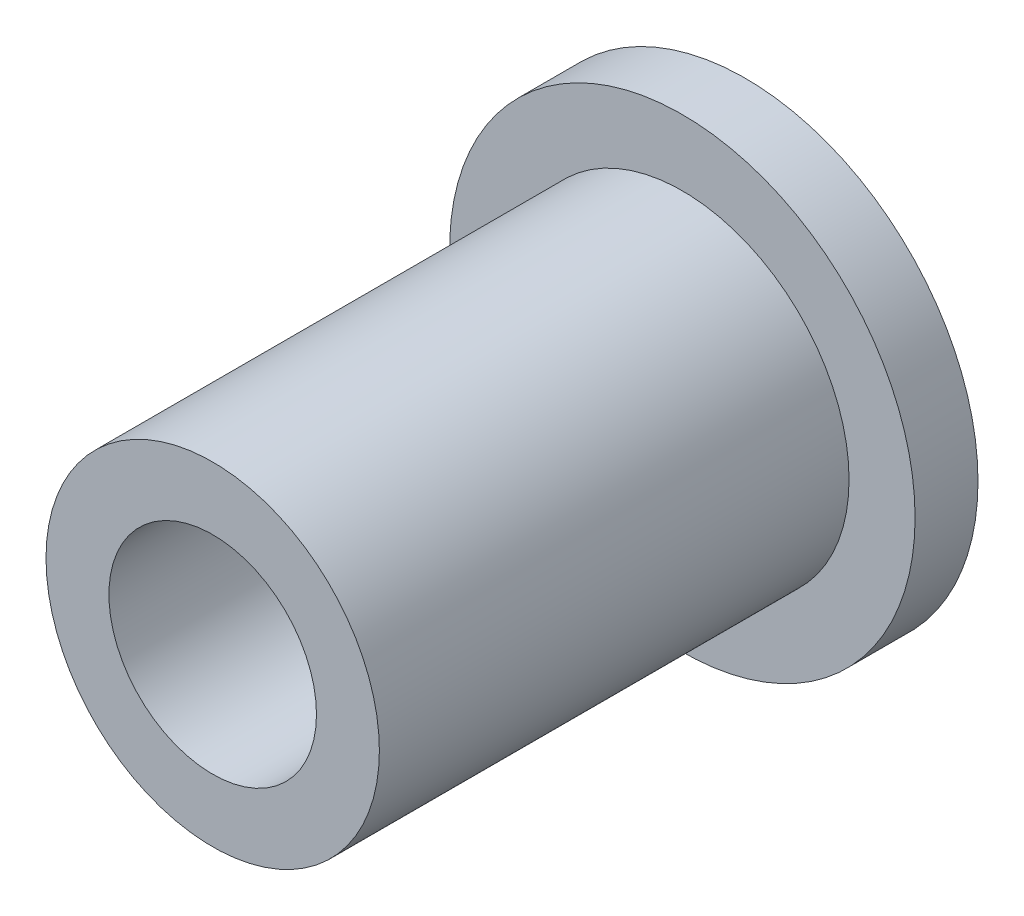
SolidWorks part; units mm, degrees
ref_plane "Front Plane" through (0, 0, 0) normal (0, 0, 1) x (1, 0, 0)
ref_plane "Top Plane" through (0, 0, 0) normal (0, 1, 0) x (1, 0, 0)
ref_plane "Right Plane" through (0, 0, 0) normal (1, 0, 0) x (0, 0, -1)
sketch "Sketch1" plane through (0, 0, 0) normal (0, 0, 1) x (1, 0, 0)
  circle A0 centre (0, 0) radius 5.55
  dimension "D1" = 11.1
base flange "Base-Flange1" sketch "Sketch1" thickness 1.5 reverse thickness direction no parameters "D1"=1
sketch "Sketch9" plane through (0, 0, 0) normal (0, 0, 1) x (1, 0, 0)
  circle A0 centre (0, 0) radius 3.975
  circle A1 centre (0, 0) radius 2.475
  dimension "D1" = 7.95
  dimension "D2" = 1.5
extrude "Boss-Extrude1" add sketch "Sketch9" along normal blind 11.2
sketch "Sketch11" plane through (0, 0, 0) normal (0, 0, 1) x (1, 0, 0)
  circle A0 centre (0, 0) radius 2.475
extrude "Cut-Extrude1" cut sketch "Sketch11" against normal through all normal cut yes
sketch "Bend-Lines1" plane through (0, 0, 0) normal (0, 1, 0) x (1, 0, 0)
sketch "Bounding-Box1" plane through (0, 0, 0) normal (0, 1, 0) x (1, 0, 0)
sheet metal parameters "Sheet-Metal(1)" thickness 1.5 parameters "D1"=1
flat pattern "Flat-Pattern(1)" [suppressed]
sketch "Bend-Lines2" plane through (0, 0, 0) normal (0, 1, 0) x (1, 0, 0)
sketch "Bounding-Box2" [suppressed] plane through (0, 0, 0) normal (0, 1, 0) x (1, 0, 0)
sheet metal parameters "Sheet-Metal(2)" thickness 1.5 parameters "D1"=1
flat pattern "Flat-Pattern(1)"
sketch "Bend-Lines2" plane through (0, 0, 0) normal (0, 1, 0) x (1, 0, 0)
sketch "Bounding-Box2" [suppressed] plane through (0, 0, 0) normal (0, 1, 0) x (1, 0, 0)
sheet metal parameters "Sheet-Metal(3)" thickness 1.5 parameters "D1"=1
flat pattern "Flat-Pattern(1)"
sketch "Bend-Lines2" plane through (0, 0, 0) normal (0, 1, 0) x (1, 0, 0)
sketch "Bounding-Box2" [suppressed] plane through (0, 0, 0) normal (0, 1, 0) x (1, 0, 0)
